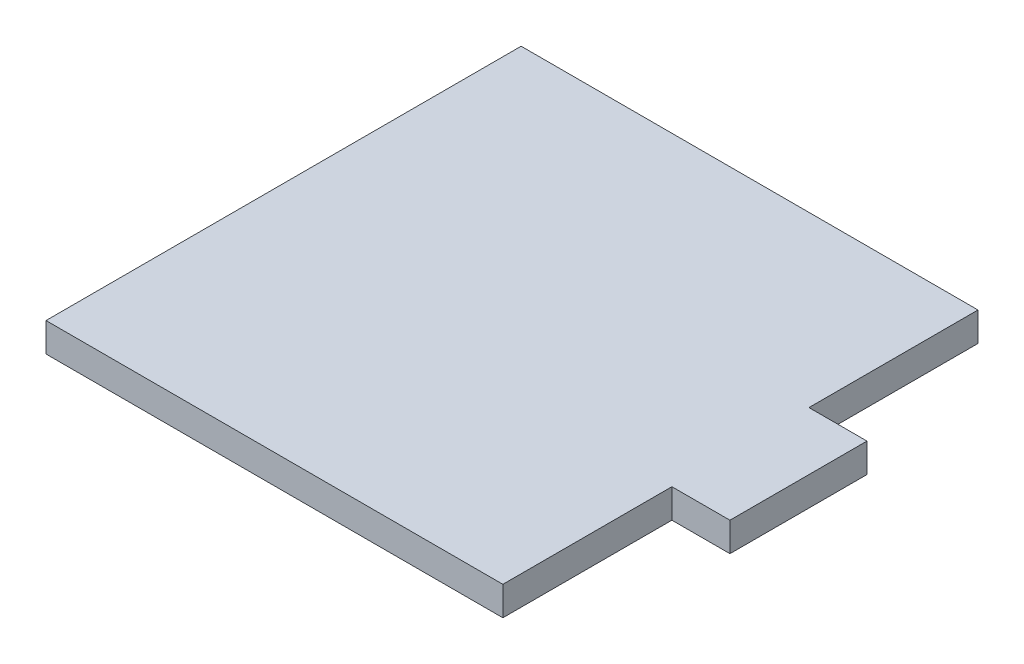
SolidWorks part; units mm, degrees
material "Cedar"
ref_plane "Front Plane" through (0, 0, 0) normal (0, 0, 1) x (1, 0, 0)
ref_plane "Top Plane" through (0, 0, 0) normal (0, 1, 0) x (1, 0, 0)
ref_plane "Right Plane" through (0, 0, 0) normal (1, 0, 0) x (0, 0, -1)
sketch "Sketch1" plane through (0, 0, 0) normal (0, 1, 0) x (1, 0, 0)
  line L0 (-25, 18.5) -> (25, 18.5)
  line L1 (25, 18.5) -> (25, 0)
  line L2 (25, 0) -> (31.35, 0)
  line L3 (31.35, 0) -> (31.35, -15)
  line L4 (31.35, -15) -> (25, -15)
  line L5 (25, -15) -> (25, -33.5)
  line L6 (25, -33.5) -> (-25, -33.5)
  line L7 (-25, -33.5) -> (-25, -15)
  line L8 (-25, -15) -> (-31.35, -15)
  line L9 (-31.35, -15) -> (-31.35, 0)
  line L10 (-31.35, 0) -> (-25, 0)
  line L11 (-25, 0) -> (-25, 18.5)
  line L12 (-25, 0) -> (-25, -15) construction
  point P11 (0, 18.5)
  point P14 (-31.35, -7.5)
  dimension "D1" = 6.35
  dimension "D2" = 15
  dimension "D3" = 50
  dimension "D4" = 52
extrude "Boss-Extrude1" add sketch "Sketch1" along normal blind 3.175 contours L11 L12 L7 L6 L5 L4 L3 L2 L1 L0 region at (0.9957, 0, 7.5)
sketch "Sketch2" plane through (0, 3.175, 0) normal (0, 1, 0) x (1, 0, 0)
  line L8 (-25, 18.5) -> (-25, -33.5)
  line L9 (-25, -33.5) -> (25, -33.5)
  line L10 (25, -33.5) -> (25, -15)
  line L11 (25, -15) -> (31.35, -15)
  line L12 (31.35, -15) -> (31.35, 0)
  line L13 (31.35, 0) -> (25, 0)
  line L14 (25, 0) -> (25, 18.5)
  line L15 (25, 18.5) -> (-25, 18.5)
  line L16 (-25, 18.5) -> (-25, -33.5)
  line L17 (-25, -33.5) -> (25, -33.5)
  line L18 (25, -33.5) -> (25, -15)
  line L19 (25, -15) -> (31.35, -15)
  line L20 (31.35, -15) -> (31.35, 0)
  line L21 (31.35, 0) -> (25, 0)
  line L22 (25, 0) -> (25, 18.5)
  line L23 (25, 18.5) -> (-25, 18.5)
  dimension "D1" = 0
equation "\"length\"= 52mm"
equation "\"w_mach\" = 50mm"
equation "\"w_tab\" = 15mm"
equation "\"t_wood\"= 0.125in"
equation "\"t_side\"= 0.25in"
equation "\"D1@Sketch1\"=\"t_side\""
equation "\"D2@Sketch1\"=\"w_tab\""
equation "\"D3@Sketch1\"=\"w_mach\""
equation "\"D4@Sketch1\"=\"length\""
equation "\"D1@Boss-Extrude1\"=\"t_wood\""
